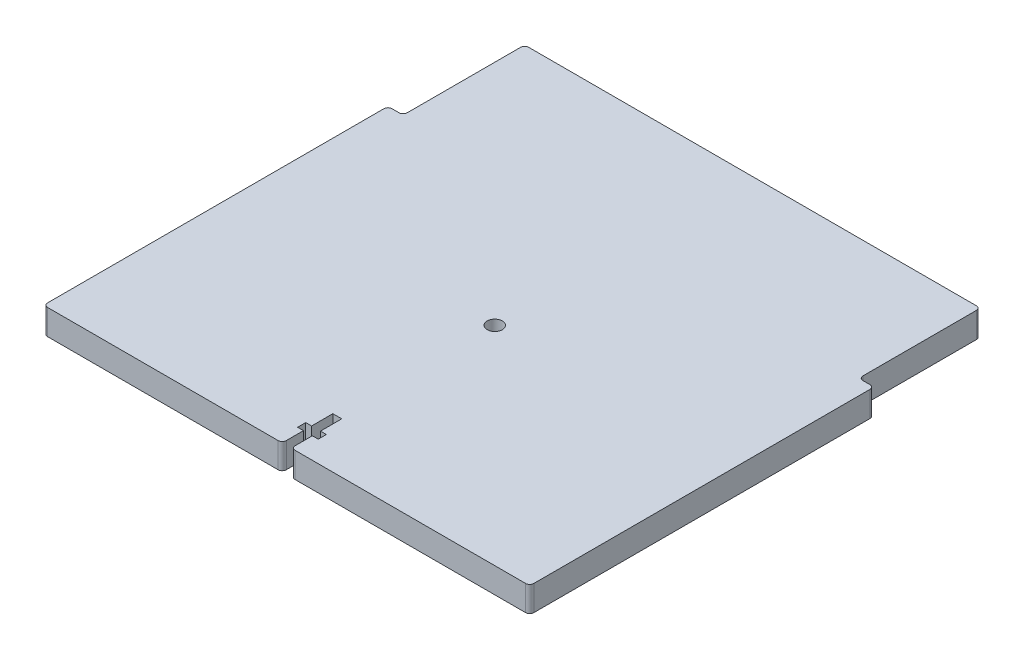
SolidWorks part; units mm, degrees
ref_plane "Front Plane" through (0, 0, 0) normal (0, 0, 1) x (1, 0, 0)
ref_plane "Top Plane" through (0, 0, 0) normal (0, 1, 0) x (1, 0, 0)
ref_plane "Right Plane" through (0, 0, 0) normal (1, 0, 0) x (0, 0, -1)
sketch "Sketch1" plane through (0, 0, 0) normal (0, 1, 0) x (1, 0, 0)
  line L1 (0, 0) -> (142.875, 0)
  line L2 (0, 107.95) -> (0, 146.05)
  line L3 (0, 146.05) -> (142.875, 146.05)
  line L4 (142.875, 107.95) -> (142.875, 146.05)
  line L5 (142.875, 0) -> (147.6375, 0)
  line L7 (142.875, 107.95) -> (147.6375, 107.95)
  line L8 (147.6375, 0) -> (147.6375, 107.95)
  line L9 (0, 0) -> (-4.7625, 0)
  line L11 (0, 107.95) -> (-4.7625, 107.95)
  line L12 (-4.7625, 0) -> (-4.7625, 107.95)
  dimension "D1" = 142.875
  dimension "D2" = 146.05
  dimension "D3" = 4.7625
  dimension "D4" = 4.7625
  dimension "D5" = 107.95
  dimension "D6" = 107.95
extrude "Boss-Extrude1" add sketch "Sketch1" along normal blind 7.9375
sketch "Sketch10" plane through (0, 7.9375, 0) normal (0, 1, 0) x (1, 0, 0)
  line L0 (71.4375, 146.05) -> (71.4375, 15.875) construction
  line L1 (70.0405, 9.2075) -> (68.199, 9.2075)
  line L3 (142.875, 146.05) -> (0, 146.05) construction
  line L4 (-4.7625, 0) -> (147.6375, 0) construction
  line L5 (70.0405, 6.6675) -> (70.0405, 0)
  line L6 (70.0405, 15.875) -> (72.8345, 15.875)
  line L7 (70.0405, 15.875) -> (70.0405, 9.2075)
  line L8 (70.0405, 0) -> (72.8345, 0)
  line L9 (72.8345, 15.875) -> (72.8345, 9.2075)
  line L12 (74.676, 6.6675) -> (72.8345, 6.6675)
  line L13 (74.676, 6.6675) -> (74.676, 9.2075)
  line L14 (74.676, 9.2075) -> (72.8345, 9.2075)
  line L15 (68.199, 6.6675) -> (68.199, 9.2075)
  line L18 (70.0405, 6.6675) -> (68.199, 6.6675)
  line L26 (72.8345, 6.6675) -> (72.8345, 0)
  point P6 (71.4375, 7.9375)
  point P11 (71.4375, 7.9375)
  dimension "D1" = 2.794
  dimension "D2" = 15.875
  dimension "D3" = 2.54
  dimension "D4" = 6.477
extrude "Cut-Extrude2" cut sketch "Sketch10" against normal through all
hole_wizard "3/16 (0.1875) Diameter Hole1" positions "Sketch11" profile "Sketch13" hole size "3/16" standard "ANSI Inch" end condition through all
sketch "Sketch11" plane through (0, 0, 0) normal (0, -1, 0) x (-1, 0, 0)
  line L0 (-142.875, -6.1905) -> (0, 136.6845) construction
  line L1 (0, 146.05) -> (0, 107.95) construction
  line L2 (-142.875, 136.6845) -> (-142.875, 109.57) construction
  line L3 (-142.875, -6.1905) -> (-147.6375, -6.1905) construction
  line L4 (4.7625, 136.6845) -> (-147.6375, 136.6845) construction
  point P7 (-71.4375, 65.247)
sketch "Sketch13" plane through (71.4375, 0, -65.247) normal (1, 0, 0) x (0, 0, -1)
  line L0 (0, 0) -> (0, 7.9375)
  line L1 (0, 7.9375) -> (2.3812, 7.9375)
  line L2 (2.3812, 7.9375) -> (2.3812, 0)
  line L5 (2.3812, 0) -> (0, 0)
  line L11 (0, -6.35) -> (0, 107.95) construction
  dimension "Thru Hole Dia." = 4.7625
  dimension "Thru Hole Depth" = 7.9375
fillet "Fillet1" radius 1.27 10 edges at (72.8345, 3.9688, 0) (70.0405, 3.9688, 0) (147.6375, 3.9688, -107.95) (142.875, 3.9688, -107.95) (142.875, 3.9688, -146.05) (0, 3.9688, -107.95) (0, 3.9688, -146.05) (-4.7625, 3.9688, -107.95) (-4.7625, 3.9688, 0) (147.6375, 3.9688, 0)
